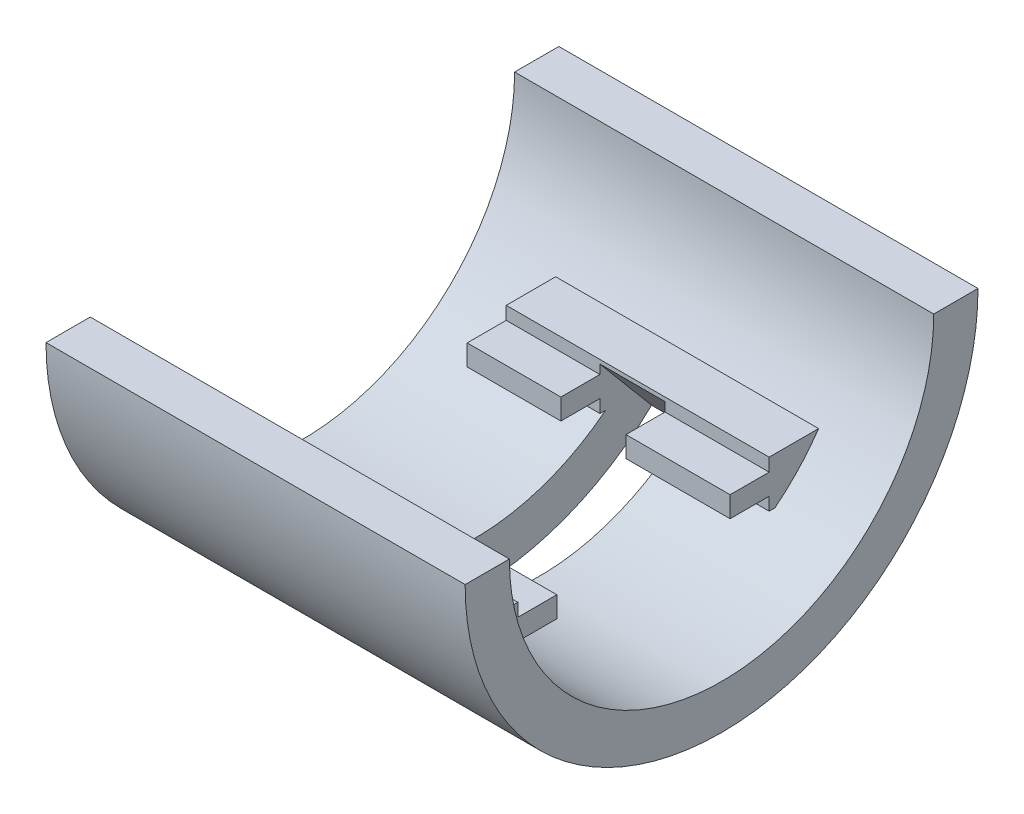
SolidWorks part; units mm, degrees
ref_plane "Front Plane" through (0, 0, 0) normal (0, 0, 1) x (1, 0, 0)
ref_plane "Top Plane" through (0, 0, 0) normal (0, 1, 0) x (1, 0, 0)
ref_plane "Right Plane" through (0, 0, 0) normal (1, 0, 0) x (0, 0, -1)
sketch "Sketch1" plane through (0, 0, 0) normal (0, 1, 0) x (1, 0, 0)
  line L1 (0, 0) -> (40.894, 0)
  line L2 (0, 0) -> (0, -25.4)
  line L3 (0, -25.4) -> (40.894, -25.4)
  line L4 (40.894, 0) -> (40.894, -25.4)
  dimension "D1" = 40.894
  dimension "D2" = 25.4
revolve "Revolve1" add sketch "Sketch1" angle 180 about L1
sketch "Sketch2" plane through (0, 0, 0) normal (0, 1, 0) x (1, 0, 0)
  line L1 (0, 0) -> (41.402, 0)
  line L2 (0, 0) -> (0, -20.701)
  line L4 (41.402, 0) -> (41.402, -20.701)
  line L5 (1.27, -20.701) -> (40.132, -20.701)
  line L8 (1.27, -20.701) -> (0, -20.701)
  line L9 (40.132, -20.701) -> (41.402, -20.701)
  line L10 (0, 0) -> (0, -21.971) construction
  line L11 (0, -21.971) -> (41.402, -21.971) construction
  line L12 (41.402, 0) -> (41.402, -21.971) construction
  line L13 (1.27, -1.27) -> (40.132, -1.27) construction
  line L14 (40.132, -1.27) -> (40.132, -20.701) construction
  line L15 (1.27, -1.27) -> (1.27, -20.701) construction
  line L16 (0, -25.4) -> (40.894, -25.4) construction
  dimension "D1" = 1.27
revolve "Cut-Revolve1" cut sketch "Sketch2" angle 360 about L1
sketch "Sketch3" plane through (0, 0, 0) normal (0, 0, 1) x (1, 0, 0)
  line L0 (40.894, -20.701) -> (40.894, 0) construction
  line L1 (33.274, -11.684) -> (7.62, -11.684)
  line L2 (33.274, -11.684) -> (33.274, -16.256)
  line L3 (33.274, -16.256) -> (7.62, -16.256)
  line L4 (7.62, -11.684) -> (7.62, -16.256)
  line L5 (40.894, 0) -> (0, 0) construction
  dimension "D1" = 7.62
  dimension "D2" = 7.62
  dimension "D3" = 4.572
  dimension "D4" = 11.684
extrude "Boss-Extrude1" add sketch "Sketch3" along normal up to surface and the other way up to surface
sketch "Sketch4" plane through (0, -11.684, 0) normal (0, 1, 0) x (1, 0, 0)
  line L0 (33.274, -17.0885) -> (33.274, 17.0885) construction
  line L1 (33.274, -12.2625) -> (7.62, -12.2625)
  line L2 (33.274, -12.2625) -> (33.274, 12.2625)
  line L3 (33.274, 12.2625) -> (7.62, 12.2625)
  line L4 (7.62, -12.2625) -> (7.62, 12.2625)
  line L5 (7.62, -17.0885) -> (7.62, 17.0885) construction
  line L6 (33.274, -17.0885) -> (7.62, -17.0885) construction
  line L7 (33.274, 17.0885) -> (7.62, 17.0885) construction
  dimension "D1" = 4.826
  dimension "D2" = 4.826
extrude "Cut-Extrude1" cut sketch "Sketch4" against normal blind 4.572
sketch "Sketch5" plane through (7.62, 0, 0) normal (-1, 0, 0) x (0, 0, 1)
  line L0 (-12.2625, -16.256) -> (-12.2625, -11.684) construction
  line L1 (-12.2625, -12.954) -> (-8.4525, -12.954)
  line L2 (-12.2625, -12.954) -> (-12.2625, -14.986)
  line L3 (-12.2625, -14.986) -> (-8.4525, -14.986)
  line L4 (-8.4525, -12.954) -> (-8.4525, -14.986)
  line L5 (12.2625, -16.256) -> (12.2625, -11.684) construction
  line L6 (12.2625, -12.954) -> (8.4525, -12.954)
  line L7 (12.2625, -12.954) -> (12.2625, -14.986)
  line L8 (12.2625, -14.986) -> (8.4525, -14.986)
  line L9 (8.4525, -12.954) -> (8.4525, -14.986)
  line L10 (17.0885, -11.684) -> (12.2625, -11.684) construction
  line L11 (-12.2625, -11.684) -> (-17.0885, -11.684) construction
  dimension "D1" = 2.032
  dimension "D2" = 3.81
  dimension "D3" = 1.27
  dimension "D4" = 1.27
  dimension "D5" = 2.032
  dimension "D6" = 3.81
extrude "Boss-Extrude2" add sketch "Sketch5" against normal up to surface (25.654 mm away) up to face at (33.274, -14.0106, -13.651)
sketch "Sketch6" plane through (0, 0, 0) normal (0, 1, 0) x (1, 0, 0)
  line L0 (40.894, -20.701) -> (0, -20.701) construction
  line L1 (7.112, -20.701) -> (11.684, -20.701)
  line L2 (7.112, -20.701) -> (7.112, -35.941)
  line L3 (7.112, -35.941) -> (11.684, -35.941)
  line L4 (11.684, -20.701) -> (11.684, -35.941)
  line L5 (0, -25.4) -> (0, -20.701) construction
  line L6 (29.21, -20.701) -> (33.782, -20.701)
  line L7 (29.21, -20.701) -> (29.21, -35.941)
  line L8 (29.21, -35.941) -> (33.782, -35.941)
  line L9 (33.782, -20.701) -> (33.782, -35.941)
  line L10 (40.894, -20.701) -> (40.894, -25.4) construction
  dimension "D1" = 7.112
  dimension "D2" = 7.112
  dimension "D3" = 4.572
  dimension "D4" = 4.572
  dimension "D5" = 15.24
  dimension "D6" = 15.24
extrude "Boss-Extrude3" [suppressed] add sketch "Sketch6" along normal blind 10.16
sketch "Sketch7" [suppressed] plane through (33.782, 0, 0) normal (1, 0, 0) x (0, 0, -1)
  line L0 (-35.941, 10.16) -> (-20.701, 10.16) construction
  line L5 (-35.941, 10.16) -> (-35.941, 0) construction
  circle A2 centre (-30.861, 5.08) radius 2.54
  dimension "D3" = 5.08
  dimension "D1" = 5.08
  dimension "D2" = 5.08
extrude "Cut-Extrude2" [suppressed] cut sketch "Sketch7" against normal blind 34.036
fillet "Fillet6" [suppressed] type full round
fillet "Fillet7" [suppressed] type full round
fillet "Fillet8" [suppressed] radius 5.08
sketch "Sketch8" plane through (0, 0, 0) normal (0, 0, 1) x (1, 0, 0)
  line L0 (40.894, -25.4) -> (40.894, 0) construction
  line L1 (23.114, -28.3258) -> (16.764, -28.3258)
  line L2 (23.114, -28.3258) -> (23.114, 2.54)
  line L3 (23.114, 2.54) -> (16.764, 2.54)
  line L4 (16.764, -28.3258) -> (16.764, 2.54)
  line L5 (0, 0) -> (40.894, 0) construction
  dimension "D1" = 6.35
  dimension "D2" = 17.78
  dimension "D3" = 2.54
revolve "Cut-Revolve2" cut sketch "Sketch8" angle 40 about L3 other way angle 40
sketch "Sketch9" plane through (40.894, 0, 0) normal (1, 0, 0) x (0, 0, -1)
  line L4 (-20.701, 0) -> (-25.4, 0)
  line L5 (25.4, 0) -> (20.701, 0)
  line L6 (-20.701, 0) -> (-25.4, 0)
  line L7 (25.4, 0) -> (20.701, 0)
  circle A2 centre (0, 0) radius 25.019
  arc A4 (-20.701, 0) -> (20.701, 0) centre (0, 0) ccw
  arc A5 (-25.4, 0) -> (25.4, 0) centre (0, 0) ccw
  arc A6 (-20.701, 0) -> (20.701, 0) centre (0, 0) ccw
  arc A7 (-25.4, 0) -> (25.4, 0) centre (0, 0) ccw
  arc M7 (-25.4, 0) -> (25.4, 0) centre (0, 0) ccw
  line M8 (25.4, 0) -> (20.701, 0)
  dimension "D2" = 0.381
  dimension "D1" = 0
extrude "Cut-Extrude3" cut sketch "Sketch9" against normal blind 45.72 contours A2 L6 M7 M8 region at (40.894, -25.0758, 0)
